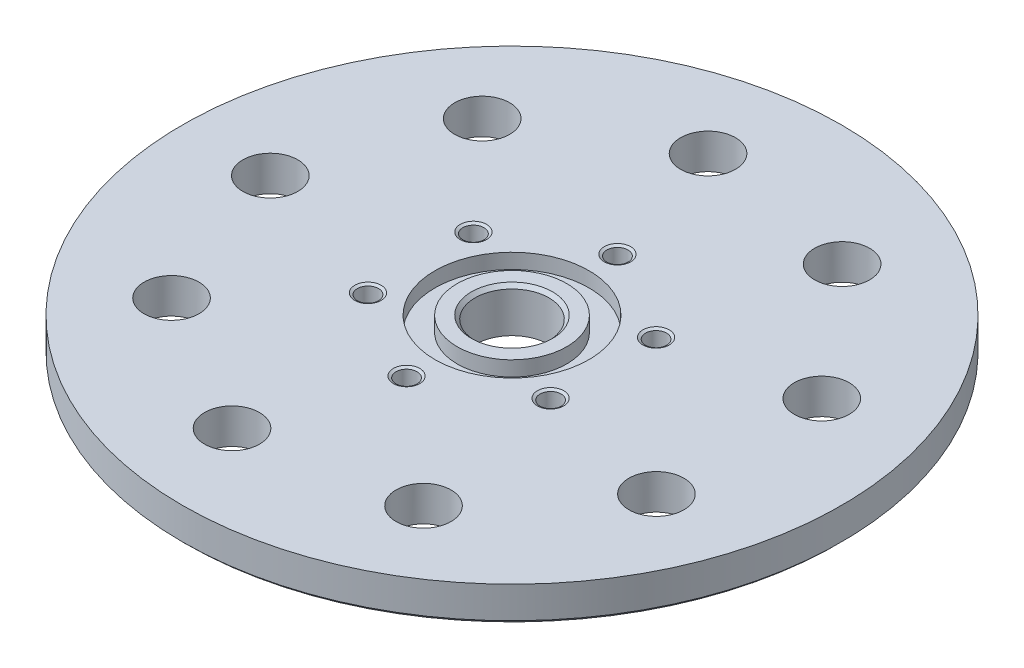
SolidWorks part; units mm, degrees
ref_plane "Front Plane" through (0, 0, 0) normal (0, 0, 1) x (1, 0, 0)
ref_plane "Top Plane" through (0, 0, 0) normal (0, 1, 0) x (1, 0, 0)
ref_plane "Right Plane" through (0, 0, 0) normal (1, 0, 0) x (0, 0, -1)
sketch "Sketch1" plane through (0, 0, 0) normal (0, 1, 0) x (1, 0, 0)
  line L1 (-63.5, -63.5) -> (63.5, -63.5)
  line L2 (-63.5, -63.5) -> (-63.5, 63.5)
  line L3 (-63.5, 63.5) -> (63.5, 63.5)
  line L4 (63.5, -63.5) -> (63.5, 63.5)
  line L5 (-63.5, -63.5) -> (63.5, 63.5) construction
  line L6 (-63.5, 63.5) -> (63.5, -63.5) construction
  point P0 (0, 0)
  dimension "D2" = 127
extrude "Boss-Extrude1" add sketch "Sketch1" along normal blind 5.08
sketch "Sketch2" plane through (0, 5.08, 0) normal (0, 1, 0) x (1, 0, 0)
  circle A0 centre (0, 0) radius 5.3467
extrude "Cut-Extrude1" cut sketch "Sketch2" against normal up to next
sketch "Sketch4" plane through (0, 5.08, 0) normal (0, 1, 0) x (1, 0, 0)
  circle A0 centre (0, 0) radius 7.9121
  circle A1 centre (0, 0) radius 11.1379
  dimension "D1" = 15.8242
  dimension "D2" = 22.2758
extrude "Cut-Extrude3" cut sketch "Sketch4" against normal blind 2.159
sketch "Sketch6" plane through (0, 5.08, 0) normal (0, 1, 0) x (1, 0, 0)
  line L0 (0, 0) -> (17.4625, -30.2459) construction
  circle A0 centre (0, 0) radius 34.925 construction
  circle A1 centre (17.4625, -30.2459) radius 3.9688
  dimension "D1" = 69.85
  dimension "D2" = 7.9375
extrude "Cut-Extrude5" cut sketch "Sketch6" against normal up to next
pattern_circular "CirPattern2" count 9 over 360 about axis through (0, 5.08, 0) along (0, 1, 0) of "Cut-Extrude5"
sketch "Sketch7" plane through (0, 5.08, 0) normal (0, 1, 0) x (1, 0, 0)
  line L0 (63.5, 63.5) -> (-63.5, 63.5) construction
  line L1 (63.5, -63.5) -> (63.5, 63.5) construction
  line L2 (0, 0) -> (63.5, 0) construction
  line L3 (0, 0) -> (0, 63.5) construction
  circle A0 centre (57.15, 57.15) radius 3.175
  circle A1 centre (0, 0) radius 38.1 construction
  circle A2 centre (57.15, -57.15) radius 3.175
  circle A3 centre (-57.15, -57.15) radius 3.175
  circle A4 centre (-57.15, 57.15) radius 3.175
  circle A5 centre (57.15, 57.15) radius 5.5562 construction
  dimension "D1" = 6.35
  dimension "D2" = 6.35
extrude "Cut-Extrude6" cut sketch "Sketch7" against normal up to next
sketch "Sketch9" plane through (0, 0, 0) normal (0, -1, 0) x (1, 0, 0)
  circle A0 centre (0, 0) radius 19.05
  circle A1 centre (0, 0) radius 5.3467
  dimension "D1" = 10.6934
  dimension "D2" = 38.1
extrude "Boss-Extrude2" add sketch "Sketch9" along normal blind 1.27
sketch "Sketch10" plane through (0, 5.08, 0) normal (0, 1, 0) x (1, 0, 0)
  line L1 (-84.358, -84.9371) -> (84.358, -84.9371)
  line L2 (-84.358, -84.9371) -> (-84.358, 84.9371)
  line L3 (-84.358, 84.9371) -> (84.358, 84.9371)
  line L4 (84.358, -84.9371) -> (84.358, 84.9371)
  line L5 (-84.358, -84.9371) -> (84.358, 84.9371) construction
  line L6 (-84.358, 84.9371) -> (84.358, -84.9371) construction
  circle A0 centre (0, 0) radius 47.625
  dimension "D1" = 95.25
extrude "Cut-Extrude7" cut sketch "Sketch10" against normal through all both and the other way through all
hole_wizard "Tapped Hole for #4-40 Helicoil3" positions "Sketch13" profile "Sketch15" tap size "#4-40" standard "Helicoil® Inch"
sketch "Sketch13" plane through (0, 5.08, 0) normal (0, 1, 0) x (1, 0, 0)
  line L0 (0, 0) -> (0, 15.24) construction
  circle A0 centre (0, 0) radius 15.24 construction
  point P0 (0, 15.24)
  dimension "D1" = 15.24
cosmetic thread "Hole Thread3" parameters "D1"=3.556, "D2"=3.7414
sketch "Sketch15" plane through (0, 5.08, -15.24) normal (1, 0, 0) x (0, 0, 1)
  line L0 (0, 0) -> (0, 6.2497)
  line L1 (0, 6.2497) -> (1.524, 5.334)
  line L2 (1.524, 5.334) -> (1.524, 0.22)
  line L3 (1.524, 0.22) -> (1.905, 0)
  line L5 (1.905, 0) -> (0, 0)
  line L6 (-1.524, 0.22) -> (-1.905, 0) construction
  line L10 (0, 6.2497) -> (-1.524, 5.334) construction
  line L11 (0, -6.35) -> (0, 107.95) construction
  dimension "Tap Drill Dia." = 3.048
  dimension "Tap Drill Depth" = 5.334
  dimension "Near C'Sink Dia." = 3.81
  dimension "Near C'Sink Angle" = 120
  dimension "Drill Angle" = 118
sketch "Sketch16" plane through (0, -1.27, 0) normal (0, -1, 0) x (1, 0, 0)
  circle A0 centre (0, 0) radius 19.05
  circle A1 centre (0, 0) radius 10.9855
  dimension "D1" = 38.1
  dimension "D2" = 21.971
extrude "Boss-Extrude3" add sketch "Sketch16" along normal blind 0.762
ref_axis "Axis1" through (0, -1.27, 0) along (0, 1, 0)
chamfer "Chamfer1" distance 0.508 angle 45 3 edges at (0, -2.032, -19.05) (0, 0, -47.625) (0, 5.08, 5.3467)
pattern_circular "CirPattern3" count 6 over 360 about axis through (0, -1.27, 0) along (0, 1, 0) of "Tapped Hole for #4-40 Helicoil3"
equation "\"AnnulusPlateThickness\"= 0.2"
equation "\"D1@Boss-Extrude1\"=\"AnnulusPlateThickness\""
equation "\"CenterRadius\"= 0.421 / 2"
equation "\"D1@Sketch2\"=\"CenterRadius\"*2"
equation "\"Basesidelength\"= 5"
equation "\"D2@Sketch1\"= \"Basesidelength\""
equation "\"D1@Sketch1\"= \"Basesidelength\""
equation "\"D1@Sketch9\"= \"CenterRadius\" * 2"
equation "\"washer ID\"= 5 / 8 - .002"
equation "\"washer OD\"= 7 / 8 + .002"
equation "\"D1@Sketch4\"= \"washer ID\""
equation "\"D2@Sketch4\"= \"washer OD\""
